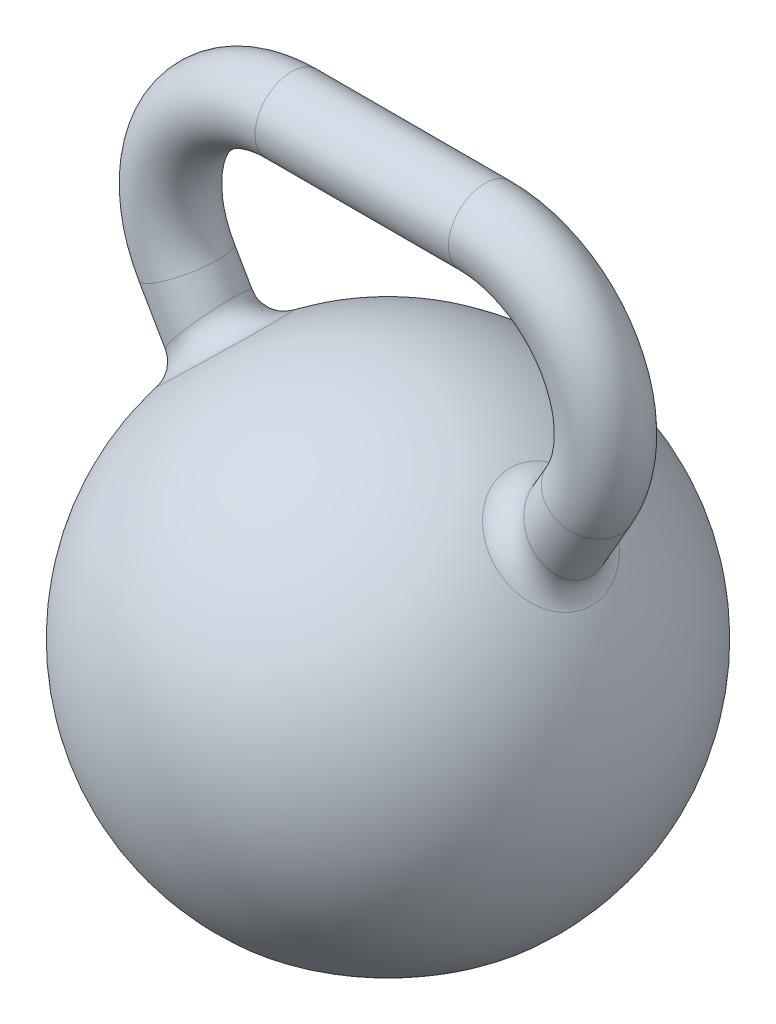
SolidWorks part; units mm, degrees
material "Gray Cast Iron"
ref_plane "Front Plane" through (0, 0, 0) normal (0, 0, 1) x (1, 0, 0)
ref_plane "Top Plane" through (0, 0, 0) normal (0, 1, 0) x (1, 0, 0)
ref_plane "Right Plane" through (0, 0, 0) normal (1, 0, 0) x (0, 0, -1)
sketch "Sketch1" plane through (0, 0, 0) normal (0, 0, 1) x (1, 0, 0)
  line L0 (0, -1752.1541) -> (0, 85855.5499) construction
  line L1 (0, -92.4) -> (76.5653, -92.4)
  line L2 (0, -92.4) -> (0, 120)
  arc A0 (76.5653, -92.4) -> (0, 120) centre (0, 0) ccw
  dimension "D1" = 120
  dimension "D2" = 92.4
revolve "Revolve1" add sketch "Sketch1" angle 360 about L0
sketch "Sketch2" plane through (0, 0, 0) normal (0, 0, 1) x (1, 0, 0)
  line L0 (0, 201.6) -> (0, -152.8631) construction
  line L1 (48, 201.6) -> (-48, 201.6)
  line L2 (-99.9615, 111.6) -> (-56.0327, 35.513)
  line L3 (99.9615, 111.6) -> (56.0327, 35.513)
  line L5 (115.55, 102.6) -> (71.6211, 26.513) construction
  line L6 (48, 219.6) -> (-48, 219.6) construction
  line L7 (-115.55, 102.6) -> (-71.6211, 26.513) construction
  line L8 (-76.5653, -92.4) -> (76.5653, -92.4) construction
  arc A0 (-48, 201.6) -> (-99.9615, 111.6) centre (-48, 141.6) ccw
  arc A1 (48, 201.6) -> (99.9615, 111.6) centre (48, 141.6) cw
  arc A2 (48, 219.6) -> (115.55, 102.6) centre (48, 141.6) cw construction
  arc A3 (-48, 219.6) -> (-115.55, 102.6) centre (-48, 141.6) ccw construction
  dimension "D3" = 96
  dimension "D4" = 78
  dimension "D1" = 60
  dimension "D2" = 312
  dimension "D5" = 18
sweep "Sweep1" add path "Sketch2" circular profile diameter 36 parameters "D3"=36
fillet "Fillet1" radius 12 3 edges at (76.5653, -92.4, 0) (-73.0483, 94.6576, 10.1923) (71.1801, 96.4945, 4.7106)
